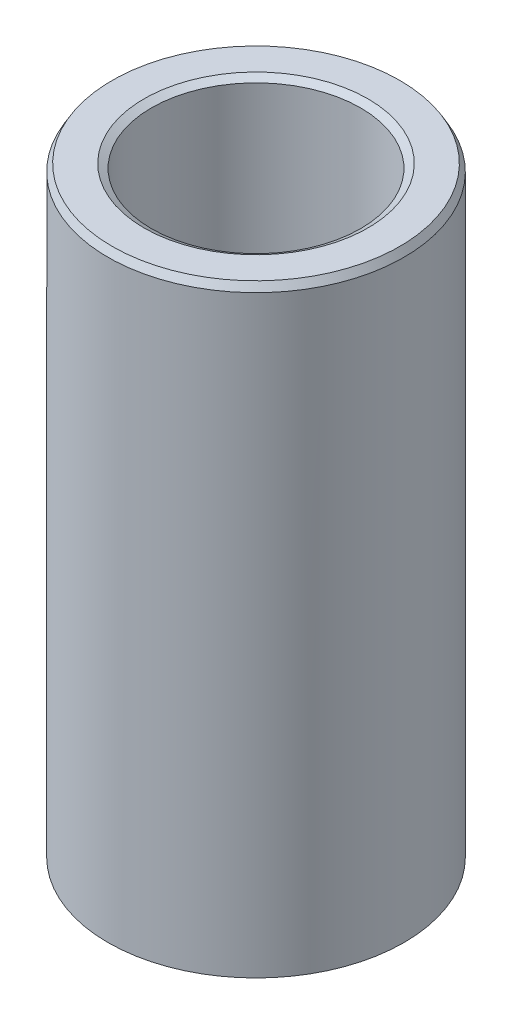
SolidWorks part; units mm, degrees
ref_plane "Front Plane" through (0, 0, 0) normal (0, 0, 1) x (1, 0, 0)
ref_plane "Top Plane" through (0, 0, 0) normal (0, 1, 0) x (1, 0, 0)
ref_plane "Right Plane" through (0, 0, 0) normal (1, 0, 0) x (0, 0, -1)
sketch "Sketch1" plane through (0, 0, 0) normal (0, 1, 0) x (1, 0, 0)
  circle A0 centre (0, 0) radius 57.5
  dimension "SLEEVE_OD" = 115
extrude "Boss-Extrude1" add sketch "Sketch1" along normal blind 235.009
sketch "Sketch2" plane through (0, 0, 0) normal (0, 1, 0) x (1, 0, 0)
  circle A0 centre (0, 0) radius 40.641
  dimension "BORE_D" = 81.2821
extrude "Cut-Extrude1" cut sketch "Sketch2" along normal through all
chamfer "Chamfer1" distance 2.8384 angle 30 4 edges at (0, 235.009, 40.641) (0, 0, 40.641) (0, 0, 57.5) (0, 235.009, 57.5) first distance on face at (0, 235.009, 40.641) first distance on face at (0, 0, 40.641) first distance on face at (0, 235.009, 57.5)
